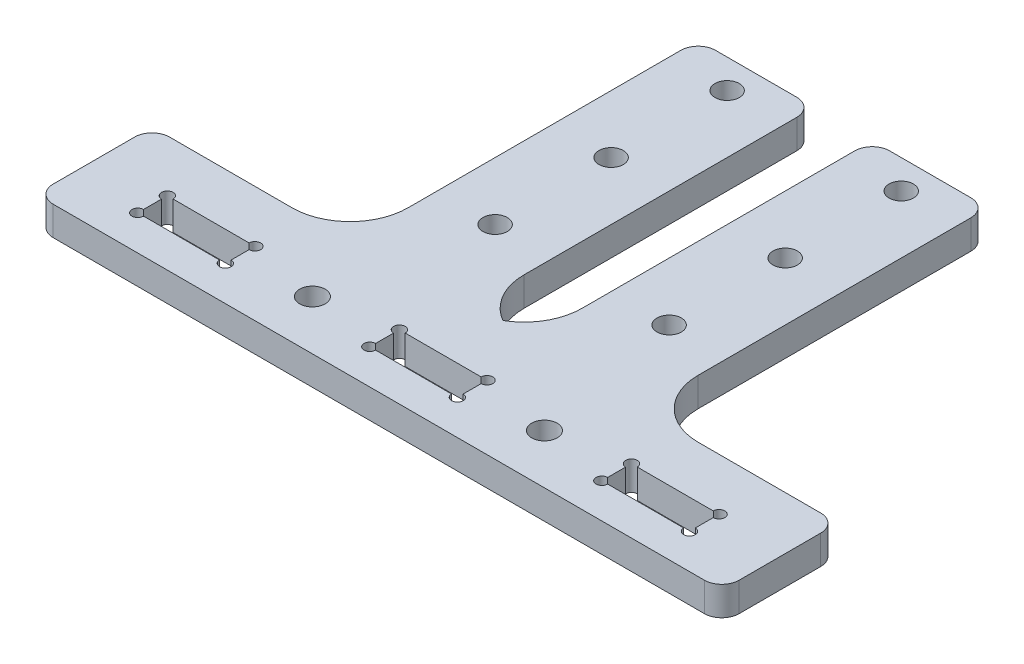
SolidWorks part; units mm, degrees
ref_plane "前视基准面" through (0, 0, 0) normal (0, 0, 1) x (1, 0, 0)
ref_plane "上视基准面" through (0, 0, 0) normal (0, 1, 0) x (1, 0, 0)
ref_plane "右视基准面" through (0, 0, 0) normal (1, 0, 0) x (0, 0, -1)
other "Configuration Table"
sketch "草图2" plane through (0, 0, 0) normal (0, 1, 0) x (1, 0, 0)
  line L0 (-103.8525, -23.4176) -> (-103.8525, 124.1824) construction
  line L1 (-163.8525, 124.1824) -> (-43.8525, 124.1824)
  line L2 (-258.8525, -23.4176) -> (-278.8525, -23.4176)
  line L3 (-278.8525, -23.4176) -> (-278.8525, 11.5824)
  line L4 (-278.8525, 11.5824) -> (-248.8697, 70.1364)
  line L5 (-258.8525, -23.4176) -> (-258.8525, 9.5824)
  line L6 (-258.8525, 9.5824) -> (-239.7507, 59.1364)
  line L7 (-239.7507, 59.1364) -> (-223.9474, 59.1364)
  line L8 (-223.9474, 59.1364) -> (-163.8525, 124.1824)
  line L9 (-169.309, 137.237) -> (-231.3021, 70.1364)
  line L11 (-248.8697, 70.1364) -> (-231.3021, 70.1364)
  line L12 (41.1646, 70.1364) -> (23.597, 70.1364)
  line L13 (-38.3961, 137.237) -> (23.597, 70.1364)
  line L14 (16.2424, 59.1364) -> (-43.8525, 124.1824)
  line L15 (-169.309, 137.237) -> (-38.3961, 137.237)
  line L16 (32.0457, 59.1364) -> (16.2424, 59.1364)
  line L17 (51.1475, 9.5824) -> (32.0457, 59.1364)
  line L18 (51.1475, -23.4176) -> (51.1475, 9.5824)
  line L19 (71.1475, 11.5824) -> (41.1646, 70.1364)
  line L20 (71.1475, -23.4176) -> (71.1475, 11.5824)
  line L21 (51.1475, -23.4176) -> (71.1475, -23.4176)
  point P13 (0, 0)
  dimension "D1" = 147.6
extrude "凸台-拉伸4" add sketch "草图2" along normal blind 5
sketch "草图3" plane through (0, 5, 0) normal (0, 1, 0) x (1, 0, 0)
  line L0 (-258.8525, -23.4176) -> (-252.8525, -23.4176)
  line L1 (-258.8525, -23.4176) -> (-258.8525, 9.5824) construction
  line L2 (-252.8525, -23.4176) -> (-252.8525, 16.8068)
  line L3 (-252.8525, 16.8068) -> (-236.5356, 59.1364)
  line L4 (-239.7507, 59.1364) -> (-223.9474, 59.1364) construction
  line L6 (-258.8525, 9.5824) -> (-239.7507, 59.1364) construction
  line L7 (-236.5356, 59.1364) -> (-239.7507, 59.1364)
  line L8 (-239.7507, 59.1364) -> (-258.8525, 9.5824)
  line L9 (-258.8525, 9.5824) -> (-258.8525, -23.4176)
  line L10 (-278.8525, -23.4176) -> (-258.8525, -23.4176) construction
  line L11 (51.1475, -23.4176) -> (45.1475, -23.4176)
  line L12 (51.1475, 9.5824) -> (51.1475, -23.4176) construction
  line L13 (51.1475, -23.4176) -> (71.1475, -23.4176) construction
  line L14 (45.1475, -23.4176) -> (45.1475, 16.8068)
  line L15 (45.1475, 16.8068) -> (28.8305, 59.1364)
  line L16 (16.2424, 59.1364) -> (32.0457, 59.1364) construction
  line L17 (32.0457, 59.1364) -> (51.1475, 9.5824) construction
  line L18 (51.1475, -23.4176) -> (51.1475, 9.5824)
  line L19 (51.1475, 9.5824) -> (32.0457, 59.1364)
  line L20 (32.0457, 59.1364) -> (28.8305, 59.1364)
  dimension "D1" = 3
  dimension "D2" = 6
  dimension "D3" = 6
  dimension "D4" = 3
extrude "凸台-拉伸5" add sketch "草图3" against normal blind 5
sketch "草图4" plane through (0, 5, 0) normal (0, 1, 0) x (1, 0, 0)
  line L0 (-252.8525, 16.8068) -> (-244.8525, -15.4176)
  line L1 (-252.8525, -23.4176) -> (-252.8525, 16.8068) construction
  line L2 (-244.8525, -15.4176) -> (-244.8525, -23.4176)
  line L3 (-244.8525, -23.4176) -> (-252.8525, -23.4176)
  line L4 (-252.8525, -23.4176) -> (-252.8525, 16.8068)
  line L5 (-278.8525, -23.4176) -> (-252.8525, -23.4176) construction
  dimension "D1" = 8
  dimension "D2" = 8
  dimension "D3" = 33.2026
extrude "凸台-拉伸6" add sketch "草图4" against normal blind 5
sketch "草图5" plane through (0, 0, 0) normal (0, -1, 0) x (1, 0, 0)
  line L0 (-278.8525, -11.5824) -> (-278.8525, 23.4176) construction
  line L1 (-278.8525, 23.4176) -> (-244.8525, 23.4176) construction
  circle A0 centre (-273.8525, 19.4176) radius 1.7
  circle A1 centre (-257.8525, 19.4176) radius 1.7
  dimension "D1" = 3.4
  dimension "D3" = 4
  dimension "D4" = 16
  dimension "D5" = 3.4
  dimension "D2" = 5
extrude "切除-拉伸1" cut sketch "草图5" against normal blind 5
sketch "草图6" plane through (0, 5, 0) normal (0, 1, 0) x (1, 0, 0)
  line L0 (45.1475, -23.4176) -> (37.1475, -23.4176)
  line L1 (45.1475, 16.8068) -> (45.1475, -23.4176) construction
  line L2 (45.1475, -23.4176) -> (71.1475, -23.4176) construction
  line L3 (37.1475, -23.4176) -> (37.1475, -15.4176)
  line L4 (37.1475, -15.4176) -> (45.1475, 16.8068)
  line L5 (28.8305, 59.1364) -> (45.1475, 16.8068) construction
  line L6 (45.1475, 16.8068) -> (45.1475, -23.4176)
  dimension "D1" = 8
  dimension "D2" = 8
extrude "凸台-拉伸7" add sketch "草图6" against normal blind 5
sketch "草图7" plane through (0, 0, 0) normal (0, -1, 0) x (1, 0, 0)
  line L0 (71.1475, 23.4176) -> (71.1475, -11.5824) construction
  line L1 (37.1475, 23.4176) -> (71.1475, 23.4176) construction
  line L2 (-103.8525, -137.237) -> (-103.8525, -102.0267) construction
  line L3 (-38.3961, -137.237) -> (-169.309, -137.237) construction
  circle A0 centre (66.1475, 19.4176) radius 1.7
  circle A1 centre (50.1475, 19.4176) radius 1.7
  dimension "D1" = 3.4
  dimension "D2" = 5
  dimension "D3" = 4
  dimension "D4" = 3.4
  dimension "D5" = 16
extrude "切除-拉伸2" cut sketch "草图7" against normal blind 5
sketch "草图8" plane through (0, 5, 0) normal (0, 1, 0) x (1, 0, 0)
  line L0 (-278.8525, -18.4176) -> (-281.8525, -18.4176)
  line L1 (-278.8525, 11.5824) -> (-278.8525, -23.4176) construction
  line L2 (-281.8525, -18.4176) -> (-281.8525, -8.4176)
  line L3 (-281.8525, -8.4176) -> (-278.8525, -8.4176)
  line L4 (-278.8525, -8.4176) -> (-278.8525, -18.4176)
  line L5 (-278.8525, -23.4176) -> (-244.8525, -23.4176) construction
  dimension "D1" = 5
  dimension "D2" = 3
  dimension "D3" = 10
extrude "凸台-拉伸8" [suppressed] add sketch "草图8" against normal blind 3
sketch "草图9" [suppressed] plane through (0, 5, 0) normal (0, 1, 0) x (1, 0, 0)
  line L0 (-278.8525, -8.4176) -> (-281.8525, -8.4176) construction
  line L1 (-278.8525, 11.5824) -> (-278.8525, -8.4176) construction
  line L2 (-278.8525, -8.4176) -> (-278.8525, -6.4176)
  line L3 (-281.8525, -18.4176) -> (-278.8525, -18.4176) construction
  line L4 (-278.8525, -18.4176) -> (-278.8525, -23.4176) construction
  line L5 (-278.8525, -20.4176) -> (-278.8525, -18.4176)
  arc A0 (-278.8525, -8.4176) -> (-278.8525, -6.4176) centre (-278.8525, -7.4176) ccw
  arc A1 (-278.8525, -18.4176) -> (-278.8525, -20.4176) centre (-278.8525, -19.4176) cw
  dimension "D1" = 1
  dimension "D2" = 1
extrude "切除-拉伸3" [suppressed] cut sketch "草图9" against normal blind 3
sketch "草图10" plane through (0, 5, 0) normal (0, 1, 0) x (1, 0, 0)
  line L0 (71.1475, -18.4176) -> (74.1475, -18.4176)
  line L1 (71.1475, -23.4176) -> (71.1475, 11.5824) construction
  line L2 (74.1475, -18.4176) -> (74.1475, -8.4176)
  line L3 (74.1475, -8.4176) -> (71.1475, -8.4176)
  line L4 (71.1475, -8.4176) -> (71.1475, -18.4176)
  line L5 (37.1475, -23.4176) -> (71.1475, -23.4176) construction
  dimension "D1" = 5
  dimension "D2" = 10
  dimension "D3" = 3
extrude "凸台-拉伸9" [suppressed] add sketch "草图10" against normal blind 3
sketch "草图11" [suppressed] plane through (0, 5, 0) normal (0, 1, 0) x (1, 0, 0)
  line L0 (74.1475, -8.4176) -> (71.1475, -8.4176) construction
  line L1 (71.1475, -8.4176) -> (71.1475, 11.5824) construction
  line L2 (71.1475, -8.4176) -> (71.1475, -6.4176)
  line L3 (71.1475, -18.4176) -> (74.1475, -18.4176) construction
  line L4 (71.1475, -23.4176) -> (71.1475, -18.4176) construction
  line L5 (71.1475, -20.4176) -> (71.1475, -18.4176)
  arc A0 (71.1475, -8.4176) -> (71.1475, -6.4176) centre (71.1475, -7.4176) cw
  arc A1 (71.1475, -18.4176) -> (71.1475, -20.4176) centre (71.1475, -19.4176) ccw
  dimension "D1" = 1
  dimension "D2" = 1
extrude "切除-拉伸4" [suppressed] cut sketch "草图11" against normal blind 3
sketch "草图12" plane through (0, 5, 0) normal (0, 1, 0) x (1, 0, 0)
  line L0 (-268.8525, -23.4176) -> (-268.8525, -26.4176)
  line L1 (-278.8525, -23.4176) -> (-244.8525, -23.4176) construction
  line L2 (-268.8525, -26.4176) -> (-253.8525, -26.4176)
  line L3 (-253.8525, -26.4176) -> (-253.8525, -23.4176)
  line L4 (-253.8525, -23.4176) -> (-268.8525, -23.4176)
  line L5 (-278.8525, 11.5824) -> (-278.8525, -23.4176) construction
  dimension "D1" = 15
  dimension "D2" = 3
  dimension "D3" = 10
extrude "凸台-拉伸10" add sketch "草图12" against normal blind 5 separate body
sketch "草图13" plane through (0, 5, 0) normal (0, 1, 0) x (1, 0, 0)
  line L0 (-278.8525, -23.4176) -> (-244.8525, -23.4176) construction
  line L1 (-253.8525, -23.4176) -> (-251.8525, -23.4176)
  line L2 (-253.8525, -26.4176) -> (-253.8525, -23.4176) construction
  line L3 (-253.8525, -23.4176) -> (-268.8525, -23.4176) construction
  line L4 (-268.8525, -23.4176) -> (-270.8525, -23.4176)
  line L5 (-268.8525, -23.4176) -> (-268.8525, -26.4176) construction
  arc A0 (-253.8525, -23.4176) -> (-251.8525, -23.4176) centre (-252.8525, -23.4176) cw
  arc A1 (-268.8525, -23.4176) -> (-270.8525, -23.4176) centre (-269.8525, -23.4176) ccw
  dimension "D1" = 1
  dimension "D2" = 1
extrude "切除-拉伸5" cut sketch "草图13" against normal blind 5
sketch "草图14" plane through (0, 0, 26.4176) normal (0, 0, 1) x (1, 0, 0)
  line L0 (-268.8525, 5) -> (-268.8525, 0)
  line L1 (-268.8525, 0) -> (-253.8525, 0)
  line L2 (-253.8525, 0) -> (-253.8525, 5)
  line L3 (-253.8525, 5) -> (-268.8525, 5)
extrude "凸台-拉伸11" add sketch "草图14" against normal blind 5
ref_plane "基准面1" [suppressed] through (-103.8525, 0, 0) normal (-1, 0, 0) x (0, 0, 1)
mirror "镜向4" about plane through (-103.8525, 0, 0) normal (-1, 0, 0) of "切除-拉伸5", "凸台-拉伸11"
sketch "草图15" plane through (0, 5, 0) normal (0, 1, 0) x (1, 0, 0)
  line L0 (-103.8525, 137.237) -> (-103.8525, 124.1824) construction
  line L1 (-38.3961, 137.237) -> (-169.309, 137.237) construction
  line L2 (-163.8525, 124.1824) -> (-43.8525, 124.1824) construction
  line L3 (-108.0177, 130.7097) -> (-103.8525, 130.7097) construction
  circle A0 centre (-163.8525, 130.7097) radius 2.2
  circle A1 centre (-43.8525, 130.7097) radius 2.2
  point P10 (-103.8525, 130.7097)
  dimension "D1" = 4.4
  dimension "D2" = 60
sketch "草图16" plane through (0, 5, 0) normal (0, 1, 0) x (1, 0, 0)
  line L0 (-103.8525, 137.237) -> (-103.8525, 85.9393) construction
  line L1 (-38.3961, 137.237) -> (-169.309, 137.237) construction
  line L2 (-200.3055, 103.6867) -> (-190.8549, 94.9554) construction
  line L3 (-169.309, 137.237) -> (-231.3021, 70.1364) construction
  line L4 (-223.9474, 59.1364) -> (-163.8525, 124.1824) construction
  line L5 (-195.5823, 99.3188) -> (-212.9484, 80.5218) construction
  line L6 (-7.3995, 103.6867) -> (-16.8502, 94.9554) construction
  line L7 (-231.3021, 70.1364) -> (-248.8697, 70.1364) construction
  line L8 (-244.8525, -23.4176) -> (-244.8525, -15.4176) construction
  circle A0 centre (-222.7242, 69.9407) radius 2.2
  circle A1 centre (-182.0082, 114.0112) radius 2.2
  circle A2 centre (-209.1522, 84.6308) radius 2.2
  circle A3 centre (1.4472, 84.6308) radius 2.2
  circle A4 centre (-25.6968, 114.0112) radius 2.2
  circle A5 centre (15.0191, 69.9407) radius 2.2
  circle A8 centre (-262.8525, 20.1364) radius 2.2
  circle A9 centre (55.1475, 20.1364) radius 2.2
  point P11 (-195.5802, 99.321)
  dimension "D1" = 4.4
  dimension "D3" = 4.4
  dimension "D4" = 20
  dimension "D5" = 4.4
  dimension "D6" = 20
  dimension "D8" = 4.4
  dimension "D2" = 40
  dimension "D9" = 50
  dimension "D10" = 18
extrude "切除-拉伸7" cut sketch "草图16" against normal blind 5
sketch "草图18" plane through (0, 5, 0) normal (0, 1, 0) x (1, 0, 0)
  line L0 (-151.4025, 132.287) -> (-151.4025, 129.187)
  line L1 (-150.4025, 128.187) -> (-137.3025, 128.187)
  line L2 (-136.3025, 129.187) -> (-136.3025, 132.287)
  line L3 (-137.3025, 133.287) -> (-150.4025, 133.287)
  line L4 (-151.3525, 130.737) -> (-136.3525, 130.737) construction
  line L5 (-38.3961, 137.237) -> (-169.309, 137.237) construction
  line L6 (-143.8525, 128.237) -> (-143.8525, 140.072) construction
  line L7 (-97.3025, 133.287) -> (-110.4025, 133.287)
  line L8 (-111.4025, 132.287) -> (-111.4025, 129.187)
  line L9 (-110.4025, 128.187) -> (-97.3025, 128.187)
  line L10 (-96.3025, 129.187) -> (-96.3025, 132.287)
  line L11 (-57.3025, 133.287) -> (-70.4025, 133.287)
  line L12 (-71.4025, 132.287) -> (-71.4025, 129.187)
  line L13 (-70.4025, 128.187) -> (-57.3025, 128.187)
  line L14 (-56.3025, 129.187) -> (-56.3025, 132.287)
  line L15 (-136.3025, 132.287) -> (-96.3025, 132.287) construction
  arc A0 (-150.4025, 133.287) -> (-151.4025, 132.287) centre (-151.4025, 133.287) ccw
  arc A1 (-151.4025, 129.187) -> (-150.4025, 128.187) centre (-151.4025, 128.187) ccw
  arc A2 (-136.3025, 132.287) -> (-137.3025, 133.287) centre (-136.3025, 133.287) ccw
  arc A3 (-137.3025, 128.187) -> (-136.3025, 129.187) centre (-136.3025, 128.187) ccw
  arc A4 (-96.3025, 132.287) -> (-97.3025, 133.287) centre (-96.3025, 133.287) ccw
  arc A5 (-110.4025, 133.287) -> (-111.4025, 132.287) centre (-111.4025, 133.287) ccw
  arc A6 (-111.4025, 129.187) -> (-110.4025, 128.187) centre (-111.4025, 128.187) ccw
  arc A7 (-97.3025, 128.187) -> (-96.3025, 129.187) centre (-96.3025, 128.187) ccw
  arc A8 (-56.3025, 132.287) -> (-57.3025, 133.287) centre (-56.3025, 133.287) ccw
  arc A9 (-70.4025, 133.287) -> (-71.4025, 132.287) centre (-71.4025, 133.287) ccw
  arc A10 (-71.4025, 129.187) -> (-70.4025, 128.187) centre (-71.4025, 128.187) ccw
  arc A11 (-57.3025, 128.187) -> (-56.3025, 129.187) centre (-56.3025, 128.187) ccw
  dimension "D5" = 2
  dimension "D1" = 6.5
  dimension "D2" = 25.4565
  dimension "D3" = 15.1
  dimension "D4" = 5.1
  dimension "D6" = 15.1
  dimension "D8" = 40
  dimension "D7" = 3
extrude "切除-拉伸8" cut sketch "草图18" against normal blind 5
sketch "草图19" plane through (0, 0, 0) normal (0, -1, 0) x (1, 0, 0)
  line L0 (-125.9525, -130.737) -> (-121.7525, -130.737) construction
  line L1 (-123.8525, -133.237) -> (-123.8525, -128.237) construction
  line L2 (-38.3961, -137.237) -> (-169.309, -137.237) construction
  line L4 (-103.8525, -137.237) -> (-103.8525, -121.9543) construction
  circle A0 centre (-123.8525, -130.737) radius 2.2
  circle A1 centre (-83.8525, -130.737) radius 2.2
  dimension "D3" = 4.4
  dimension "D1" = 6.5
  dimension "D2" = 45.4565
extrude "切除-拉伸9" cut sketch "草图19" against normal blind 5
sketch "草图20" plane through (0, 0, 0) normal (0, -1, 0) x (1, 0, 0)
  line L0 (-231.3021, -70.1364) -> (-248.8697, -70.1364) construction
  line L2 (41.1646, -70.1364) -> (23.597, -70.1364) construction
  line L4 (29.6015, -57.1364) -> (15.3672, -57.1364)
  line L5 (-248.8697, -70.1364) -> (-246.3094, -75.1364)
  line L6 (-246.3094, -75.1364) -> (-233.4899, -75.1364)
  line L7 (-233.4899, -75.1364) -> (-171.4968, -142.237)
  line L8 (-171.4968, -142.237) -> (-36.2082, -142.237)
  line L9 (-36.2082, -142.237) -> (25.7849, -75.1364)
  line L10 (25.7849, -75.1364) -> (38.6044, -75.1364)
  line L11 (38.6044, -75.1364) -> (41.1646, -70.1364)
  line L12 (71.1475, -11.5824) -> (41.1646, -70.1364) construction
  line L13 (23.597, -70.1364) -> (-38.3961, -137.237) construction
  line L14 (-38.3961, -137.237) -> (-169.309, -137.237) construction
  line L15 (-248.8697, -70.1364) -> (-278.8525, -11.5824) construction
  line L16 (-169.309, -137.237) -> (-231.3021, -70.1364) construction
  line L17 (28.8305, -59.1364) -> (45.1475, -16.8068) construction
  line L18 (15.3672, -57.1364) -> (-44.7277, -122.1824)
  line L19 (-44.7277, -122.1824) -> (-162.9774, -122.1824)
  line L20 (-162.9774, -122.1824) -> (-223.0723, -57.1364)
  line L21 (-223.0723, -57.1364) -> (-237.3065, -57.1364)
  line L22 (-252.8525, -16.8068) -> (-236.5356, -59.1364) construction
  line L23 (-237.3065, -57.1364) -> (-236.5356, -59.1364)
  line L24 (-236.5356, -59.1364) -> (-223.9474, -59.1364)
  line L25 (-223.9474, -59.1364) -> (-163.8525, -124.1824)
  line L26 (-163.8525, -124.1824) -> (-43.8525, -124.1824)
  line L27 (-43.8525, -124.1824) -> (16.2424, -59.1364)
  line L28 (16.2424, -59.1364) -> (28.8305, -59.1364)
  line L29 (28.8305, -59.1364) -> (29.6015, -57.1364)
  line L30 (-248.8697, -70.1364) -> (-231.3021, -70.1364)
  line L31 (-231.3021, -70.1364) -> (-169.309, -137.237)
  line L32 (-169.309, -137.237) -> (-38.3961, -137.237)
  line L33 (-38.3961, -137.237) -> (23.597, -70.1364)
  line L34 (23.597, -70.1364) -> (41.1646, -70.1364)
  dimension "D1" = 5
  dimension "D2" = 5
  dimension "D3" = 5
  dimension "D4" = 5
  dimension "D5" = 5
  dimension "D6" = 2
  dimension "D7" = 2
  dimension "D8" = 2
  dimension "D9" = 2
  dimension "D10" = 2
extrude "凸台-拉伸12" add sketch "草图20" against normal blind 5
fillet "圆角1" radius 2 6 edges at (37.1475, 2.5, 15.4176) (37.1475, 2.5, 23.4176) (71.1475, 2.5, 23.4176) (-244.8525, 2.5, 23.4176) (-244.8525, 2.5, 15.4176) (-278.8525, 2.5, 23.4176)
sketch "草图21" plane through (0, 0, 0) normal (0, -1, 0) x (1, 0, 0)
  line L0 (-171.4968, -142.237) -> (-36.2082, -142.237) construction
  line L1 (-162.9774, -142.237) -> (-297.2102, -142.237)
  line L2 (-162.9774, -142.237) -> (-162.9774, 46.7702)
  line L3 (-162.9774, 46.7702) -> (-297.2102, 46.7702)
  line L4 (-297.2102, -142.237) -> (-297.2102, 46.7702)
  line L6 (-44.7277, -142.237) -> (121.5418, -142.237)
  line L7 (-44.7277, -142.237) -> (-44.7277, 34.1158)
  line L8 (-44.7277, 34.1158) -> (121.5418, 34.1158)
  line L9 (121.5418, -142.237) -> (121.5418, 34.1158)
  point P10 (-165.6962, -142.237)
extrude "切除-拉伸10" cut sketch "草图21" against normal through all
sketch "草图22" plane through (0, 0, 0) normal (0, -1, 0) x (1, 0, 0)
  line L0 (-162.9774, -142.237) -> (-44.7277, -142.237) construction
  line L1 (-128.8525, -142.237) -> (-108.8525, -142.237)
  line L2 (-128.8525, -142.237) -> (-128.8525, -202.237)
  line L3 (-128.8525, -202.237) -> (-108.8525, -202.237)
  line L4 (-108.8525, -142.237) -> (-108.8525, -202.237)
  line L5 (-103.8525, -142.237) -> (-103.8525, -201.5201) construction
  line L6 (-78.8525, -202.237) -> (-98.8525, -202.237)
  line L7 (-98.8525, -142.237) -> (-98.8525, -202.237)
  line L8 (-78.8525, -142.237) -> (-98.8525, -142.237)
  line L9 (-78.8525, -142.237) -> (-78.8525, -202.237)
  circle A0 centre (-118.8525, -197.237) radius 2.1
  circle A1 centre (-118.8525, -177.237) radius 2.1
  circle A2 centre (-118.8525, -157.237) radius 2.1
  circle A3 centre (-88.8525, -197.237) radius 2.1
  circle A4 centre (-88.8525, -177.237) radius 2.1
  circle A5 centre (-88.8525, -157.237) radius 2.1
  point P6 (-103.8525, -142.237)
  dimension "D3" = 10
  dimension "D5" = 4.2
  dimension "D1" = 25
  dimension "D2" = 20
  dimension "D4" = 5
  dimension "D6" = 60
  dimension "D8" = 20
  dimension "D7" = 3
extrude "凸台-拉伸13" add sketch "草图22" against normal through all
fillet "圆角2" radius 10 4 edges at (-78.8525, 2.5, -142.237) (-128.8525, 2.5, -142.237) (-108.8525, 2.5, -142.237) (-98.8525, 2.5, -142.237)
fillet "圆角3" radius 3 8 edges at (-162.9774, 2.5, -122.1824) (-44.7277, 2.5, -122.1824) (-44.7277, 2.5, -142.237) (-162.9774, 2.5, -142.237) (-128.8525, 2.5, -202.237) (-108.8525, 2.5, -202.237) (-98.8525, 2.5, -202.237) (-78.8525, 2.5, -202.237)
